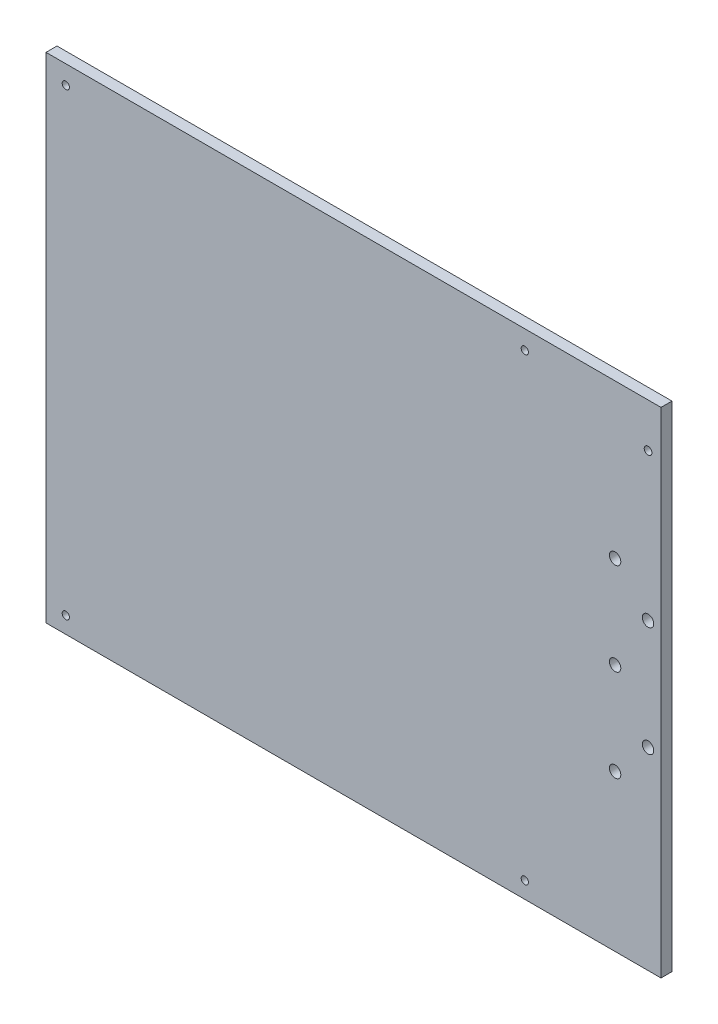
SolidWorks part; units mm, degrees
material "Lega 1060"
ref_plane "Piano frontale" through (0, 0, 0) normal (0, 0, 1) x (1, 0, 0)
ref_plane "Piano superiore" through (0, 0, 0) normal (0, 1, 0) x (1, 0, 0)
ref_plane "Piano destro" through (0, 0, 0) normal (1, 0, 0) x (0, 0, -1)
sketch "Schizzo1" plane through (0, 0, 0) normal (0, 0, 1) x (1, 0, 0)
  line L1 (0, 20) -> (-280, 20)
  line L2 (0, 20) -> (0, 245)
  line L3 (0, 245) -> (-280, 245)
  line L4 (-280, 20) -> (-280, 245)
  dimension "D1" = 280
  dimension "D2" = 225
  dimension "D3" = 20
extrude "Estrusione-Estrusione1" add sketch "Schizzo1" along normal blind 5
hole_wizard "Foro filettato M4-1" positions "Schizzo11" profile "Schizzo10" tap size "M4" standard "ISO" end condition up to next
sketch "Schizzo11" plane through (0, 0, 0) normal (0, 0, -1) x (-1, 0, 0)
  line L0 (280, 20) -> (0, 20) construction
  point P0 (271, 27.5)
  point P2 (62, 27.5)
  point P4 (271, 236.5)
  point P6 (62, 236.5)
  dimension "D1" = 7.5
  dimension "D2" = 209
  dimension "D3" = 209
  dimension "D4" = 9
sketch "Schizzo10" plane through (-271, 27.5, 0) normal (1, 0, 0) x (0, 1, 0)
  line L0 (0, 0) -> (0, 5)
  line L1 (0, 5) -> (1.65, 5)
  line L2 (1.65, 5) -> (1.65, 0)
  line L5 (1.65, 0) -> (0, 0)
  line L11 (0, -6.35) -> (0, 107.95) construction
  dimension "Thru Tap Drill Dia." = 3.3
  dimension "Thru Tap Drill Depth" = 5
cosmetic thread "Filettatura del foro2" parameters "D2"=4
cosmetic thread "Filettatura del foro4" parameters "D2"=4
cosmetic thread "Filettatura del foro5" parameters "D2"=4
cosmetic thread "Filettatura del foro6" parameters "D2"=4
sketch "Schizzo12" plane through (0, 0, 0) normal (0, 0, -1) x (-1, 0, 0)
  line L0 (0, 20) -> (0, 245) construction
  line L1 (0, 245) -> (280, 245) construction
  line L2 (5.8957, 107.9884) -> (5.8957, 157.9884) construction
  circle A0 centre (5.8957, 107.9884) radius 2.6
  circle A1 centre (5.8957, 157.9884) radius 2.6
  circle A2 centre (20.8957, 90.9884) radius 2.6
  circle A3 centre (20.8957, 132.9884) radius 2.6
  circle A4 centre (20.8957, 174.9884) radius 2.6
  circle A5 centre (5.8957, 225) radius 1.75
  dimension "D5" = 3.5
  dimension "D1" = 50
  dimension "D2" = 84
  dimension "D3" = 5.8957
  dimension "D4" = 20.8957
  dimension "D6" = 20
extrude "Taglio-Estrusione1" cut sketch "Schizzo12" against normal blind 10
